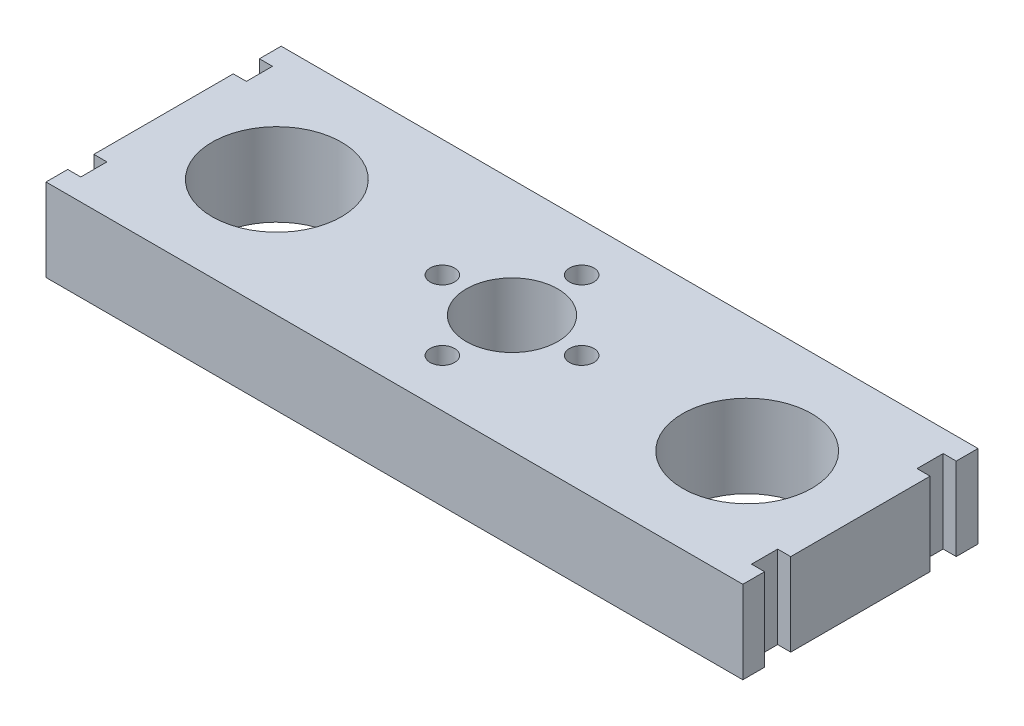
SolidWorks part; units mm, degrees
ref_plane "前视基准面" through (0, 0, 0) normal (0, 0, 1) x (1, 0, 0)
ref_plane "上视基准面" through (0, 0, 0) normal (0, 1, 0) x (1, 0, 0)
ref_plane "右视基准面" through (0, 0, 0) normal (1, 0, 0) x (0, 0, -1)
sketch "草图1" plane through (0, 0, 0) normal (0, 1, 0) x (1, 0, 0)
  line L1 (-40, 13.5) -> (40, 13.5)
  line L2 (-40, 13.5) -> (-40, -13.5)
  line L3 (-40, -13.5) -> (40, -13.5)
  line L4 (40, 13.5) -> (40, -13.5)
  line L5 (-40, 13.5) -> (40, -13.5) construction
  line L6 (-40, -13.5) -> (40, 13.5) construction
  point P0 (0, 0)
  dimension "D1" = 80
  dimension "D2" = 27
extrude "凸台-拉伸1" add sketch "草图1" along normal blind 9.5
sketch "草图2" plane through (0, 0, 0) normal (0, -1, 0) x (1, 0, 0)
  line L0 (-40, 0) -> (40, 0) construction
  line L1 (-40, -13.5) -> (-40, 13.5) construction
  line L2 (40, 13.5) -> (40, -13.5) construction
ref_plane "基准面1" through (0, 0, 0) normal (0, 0, 1) x (1, 0, 0)
sketch "草图3" plane through (0, 9.5, 0) normal (0, 1, 0) x (1, 0, 0)
  line L0 (-14.85, 0) -> (14.85, 0) construction
  line L1 (0, 13.5) -> (0, -13.5) construction
  line L2 (40, 13.5) -> (-40, 13.5) construction
  line L3 (-40, -13.5) -> (40, -13.5) construction
  circle A0 centre (-27, 0) radius 7.425
  circle A1 centre (27, 0) radius 7.425
  dimension "D1" = 14.85
  dimension "D2" = 54
extrude "切除-拉伸1" cut sketch "草图3" against normal through all contours A1 | A0
sketch "草图4" plane through (0, 9.5, 0) normal (0, 1, 0) x (1, 0, 0)
  line L0 (-40, 0) -> (40, 0) construction
  circle A0 centre (0, 0) radius 5.25
  dimension "D1" = 10.5
extrude "切除-拉伸2" cut sketch "草图4" against normal through all
sketch "草图5" plane through (0, 9.5, 0) normal (0, 1, 0) x (1, 0, 0)
  circle A4 centre (8, 0) radius 1.4
  circle A8 centre (-8, 0) radius 1.4
  circle A9 centre (0, 8) radius 1.4
  circle A10 centre (0, -8) radius 1.4
  dimension "D1" = 2.8
extrude "切除-拉伸3" cut sketch "草图5" against normal through all
ref_plane "基准面2" through (0, 4.5, 0) normal (0, 1, 0) x (1, 0, 0)
sketch "草图6" plane through (0, 4.5, 0) normal (0, 1, 0) x (1, 0, 0)
  line L0 (-40, 9.5) -> (40, 9.5) construction
  line L1 (-40, 13.5) -> (-40, -13.5) construction
  line L2 (40, -13.5) -> (40, 13.5) construction
  line L3 (-40, -9.5) -> (40, -9.5) construction
  line L4 (-40, -13.5) -> (40, -13.5) construction
  line L5 (40, 13.5) -> (-40, 13.5) construction
  dimension "D1" = 4
  dimension "D2" = 4
sketch "草图7" plane through (0, 9.5, 0) normal (0, 1, 0) x (1, 0, 0)
  line L0 (40, -13.5) -> (40, 13.5) construction
  line L1 (40, 11.0016) -> (38.5, 11.0016)
  line L2 (40, 11.0016) -> (40, 8.0016)
  line L3 (40, 8.0016) -> (38.5, 8.0016)
  line L4 (38.5, 11.0016) -> (38.5, 8.0016)
  line L13 (40, -7.9999) -> (38.5, -7.9999)
  line L14 (40, -7.9999) -> (40, -10.9999)
  line L15 (40, -10.9999) -> (38.5, -10.9999)
  line L16 (38.5, -7.9999) -> (38.5, -10.9999)
  line L17 (-40, 13.5) -> (-40, -13.5) construction
  line L18 (-40, 11.0016) -> (-38.5, 11.0016)
  line L19 (-40, 11.0016) -> (-40, 8.0016)
  line L20 (-40, 8.0016) -> (-38.5, 8.0016)
  line L21 (-38.5, 11.0016) -> (-38.5, 8.0016)
  line L23 (-40, -8.0068) -> (-38.5, -8.0068)
  line L24 (-40, -8.0068) -> (-40, -11.0068)
  line L25 (-40, -11.0068) -> (-38.5, -11.0068)
  line L26 (-38.5, -8.0068) -> (-38.5, -11.0068)
  dimension "D1" = 1.5
  dimension "D2" = 3
  dimension "D3" = 3
  dimension "D4" = 1.5
  dimension "D5" = 1.5
  dimension "D6" = 1.5
  dimension "D7" = 3
  dimension "D8" = 1.5
  dimension "D9" = 3
  dimension "D10" = 1.5
extrude "切除-拉伸4" cut sketch "草图7" against normal through all
